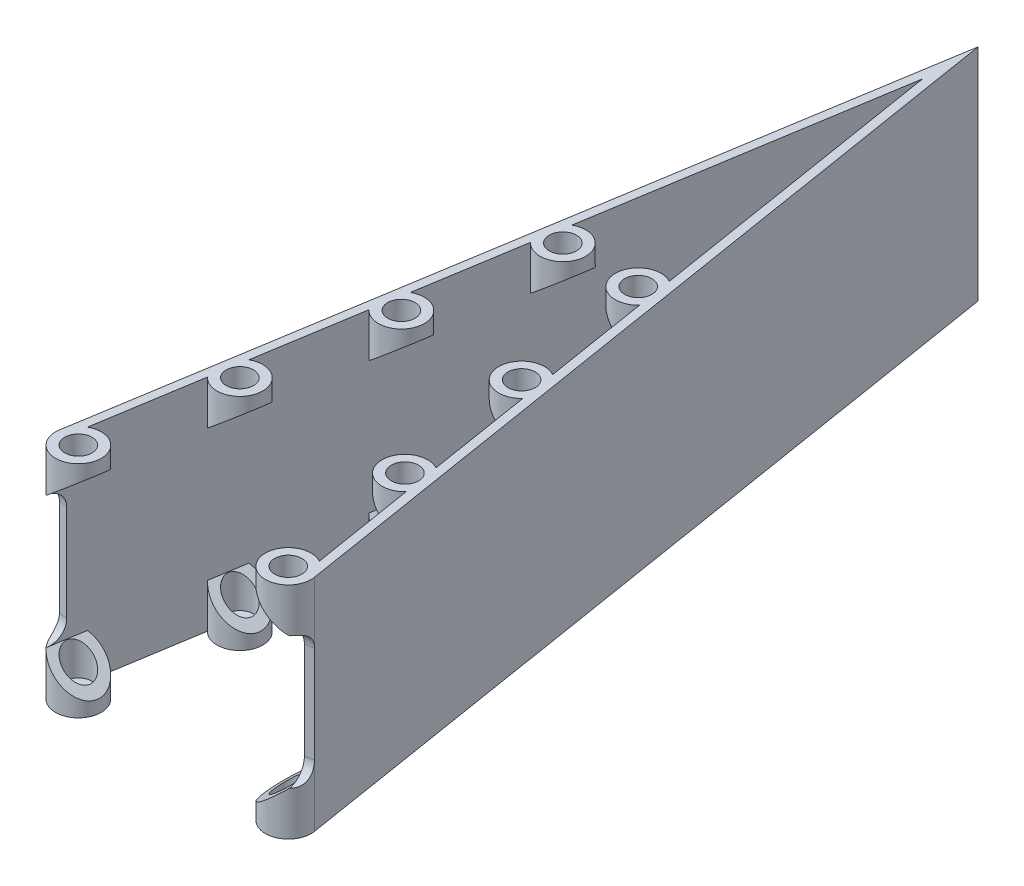
SolidWorks part; units mm, degrees
ref_plane "Front Plane" through (0, 0, 0) normal (0, 0, 1) x (1, 0, 0)
ref_plane "Top Plane" through (0, 0, 0) normal (0, 1, 0) x (1, 0, 0)
ref_plane "Right Plane" through (0, 0, 0) normal (1, 0, 0) x (0, 0, -1)
sketch "Sketch1" plane through (0, 0, 0) normal (0, 1, 0) x (1, 0, 0)
  line L0 (-13.5, 0) -> (13.5, 0) construction
  line L1 (-13.5, 0) -> (0, 83.7185)
  line L2 (0, 83.7185) -> (13.5, 0)
  line L3 (13.5, 0) -> (14.4872, 0.1592)
  line L4 (14.4872, 0.1592) -> (0, 90)
  line L5 (0, 90) -> (-14.4872, 0.1592)
  line L6 (-14.4872, 0.1592) -> (-13.5, 0)
  point P2 (0, 0)
  dimension "D1" = 90
  dimension "D2" = 90
  dimension "D4" = 1
  dimension "D5" = 27
  dimension "D3" = 90
extrude "Boss-Extrude1" add sketch "Sketch1" along normal blind 25
sketch "Sketch2" plane through (0, 0, 0) normal (0, 1, 0) x (1, 0, 0)
  line L0 (0, -1000) -> (0, 49000) construction
  line L1 (0, 83.7185) -> (13.5, 0) construction
  line L2 (0, 83.7185) -> (13.5, 0) construction
  line L3 (11.9204, -0.2547) -> (13.5, 0) construction
  line L4 (13.5, 0) -> (14.4872, 0.1592) construction
  line L5 (14.4872, 0.1592) -> (0, 90) construction
  line L6 (14.4872, 0.1592) -> (0, 90) construction
  circle A0 centre (11.9204, -0.2547) radius 2.6
  circle A1 centre (11.9204, -0.2547) radius 1.55
  circle A22 centre (9.3732, 15.5412) radius 1.55
  circle A23 centre (9.3732, 15.5412) radius 2.6
  circle A24 centre (6.8261, 31.3372) radius 1.55
  circle A25 centre (6.8261, 31.3372) radius 2.6
  circle A26 centre (4.2789, 47.1331) radius 1.55
  circle A27 centre (4.2789, 47.1331) radius 2.6
  circle A28 centre (-4.2789, 47.1331) radius 2.6
  circle A29 centre (-4.2789, 47.1331) radius 1.55
  circle A30 centre (-6.8261, 31.3372) radius 2.6
  circle A31 centre (-6.8261, 31.3372) radius 1.55
  circle A32 centre (-9.3732, 15.5412) radius 2.6
  circle A33 centre (-9.3732, 15.5412) radius 1.55
  circle A34 centre (-11.9204, -0.2547) radius 2.6
  circle A35 centre (-11.9204, -0.2547) radius 1.55
  dimension "D1" = 5.2
  dimension "D2" = 3.1
  dimension "D4" = 16
  dimension "D3" = 4
extrude "Boss-Extrude3" add sketch "Sketch2" along normal blind 5
sketch "Sketch4" plane through (0.3421, 0, 2.1218) normal (0.1592, 0, 0.9872) x (0.9872, 0, -0.1592)
  line L0 (9.1278, 5) -> (9.1278, 0) construction
  line L1 (14.3278, 5) -> (9.1278, 5) construction
  line L2 (13.3278, 25) -> (13.3278, 0) construction
  line L3 (9.1278, 5) -> (9.1278, 0) construction
  line L4 (14.3278, 5) -> (9.1278, 5) construction
  line L5 (13.3278, 25) -> (13.3278, 0) construction
  line L6 (13.3278, 5) -> (9.1278, 1.4758)
  line L7 (13.3278, 5) -> (9.1278, 5)
  line L8 (9.1278, 5) -> (9.1278, 1.4758)
  dimension "D1" = 40
extrude "Cut-Extrude1" cut sketch "Sketch4" against normal up to surface and the other way through all contours L7 L8 L6 up to face at (-8.5675, 5, -30.5881)
sketch "Sketch5" plane through (-0.3421, 0, 2.1218) normal (-0.1592, 0, 0.9872) x (0.9872, 0, 0.1592)
  line L0 (-9.1278, 0) -> (-9.1278, 5) construction
  line L1 (-9.1278, 5) -> (-14.3278, 5) construction
  line L2 (-13.3278, 25) -> (-13.3278, 0) construction
  line L3 (-9.1278, 0) -> (-9.1278, 5) construction
  line L4 (-9.1278, 5) -> (-14.3278, 5) construction
  line L5 (-13.3278, 25) -> (-13.3278, 0) construction
  line L6 (-13.3278, 5) -> (-9.1278, 1.4758)
  line L7 (-13.3278, 5) -> (-9.1278, 5)
  line L8 (-9.1278, 5) -> (-9.1278, 1.4758)
  dimension "D1" = 40
extrude "Cut-Extrude2" cut sketch "Sketch5" against normal up to surface and the other way through all contours L8 L7 L6 up to face at (8.5675, 5, -30.5881)
ref_plane "Plane1" through (0, 12.5, 0) normal (0, 1, 0) x (1, 0, 0)
mirror "Mirror2" about plane through (0, 12.5, 0) normal (0, 1, 0) of "Cut-Extrude2", "Cut-Extrude1", "Boss-Extrude3"
fillet "Fillet1" radius 2 4 edges at (13.9936, 5, -0.0796) (13.9936, 20, -0.0796) (-13.9936, 5, -0.0796) (-13.9936, 20, -0.0796)
sketch "Sketch6" plane through (0, 0, 0) normal (0, -1, 0) x (1, 0, 0)
  arc A1 (14.4872, -0.1592) -> (13.1737, -2.0233) centre (11.9204, 0.2547) ccw construction
  arc A2 (11.2791, -13.7727) -> (10.6266, -17.8192) centre (9.3732, -15.5412) ccw construction
  arc A5 (8.7319, -29.5686) -> (8.0794, -33.6151) centre (6.8261, -31.3372) ccw construction
  arc A6 (6.1847, -45.3646) -> (5.5322, -49.4111) centre (4.2789, -47.1331) ccw construction
  arc A10 (-5.5322, -49.4111) -> (-6.1847, -45.3646) centre (-4.2789, -47.1331) ccw construction
  arc A11 (14.4872, -0.1592) -> (13.1737, -2.0233) centre (11.9204, 0.2547) ccw
  arc A12 (11.2791, -13.7727) -> (10.6266, -17.8192) centre (9.3732, -15.5412) ccw
  arc A13 (-8.0794, -33.6151) -> (-8.7319, -29.5686) centre (-6.8261, -31.3372) ccw construction
  arc A14 (-10.6266, -17.8192) -> (-11.2791, -13.7727) centre (-9.3732, -15.5412) ccw construction
  arc A15 (8.7319, -29.5686) -> (8.0794, -33.6151) centre (6.8261, -31.3372) ccw
  arc A16 (6.1847, -45.3646) -> (5.5322, -49.4111) centre (4.2789, -47.1331) ccw
  arc A17 (-13.1737, -2.0233) -> (-14.4872, -0.1592) centre (-11.9204, 0.2547) ccw construction
  arc A18 (-5.5322, -49.4111) -> (-6.1847, -45.3646) centre (-4.2789, -47.1331) ccw
  arc A19 (-8.0794, -33.6151) -> (-8.7319, -29.5686) centre (-6.8261, -31.3372) ccw
  circle A22 centre (4.2789, -47.1331) radius 2.6
  circle A24 centre (6.8261, -31.3372) radius 2.6
  circle A27 centre (9.3732, -15.5412) radius 2.6
  circle A28 centre (11.9204, 0.2547) radius 2.6
  arc A30 (-10.6266, -17.8192) -> (-11.2791, -13.7727) centre (-9.3732, -15.5412) ccw
  arc A31 (-13.1737, -2.0233) -> (-14.4872, -0.1592) centre (-11.9204, 0.2547) ccw
  circle A32 centre (-11.9204, 0.2547) radius 2.6
  circle A33 centre (-9.3732, -15.5412) radius 2.6
  circle A34 centre (-6.8261, -31.3372) radius 2.6
  circle A35 centre (-4.2789, -47.1331) radius 2.6
extrude "Boss-Extrude4" add sketch "Sketch6" against normal blind 1
equation "\"D2@Sketch1\"=\"D1@Sketch1\""
